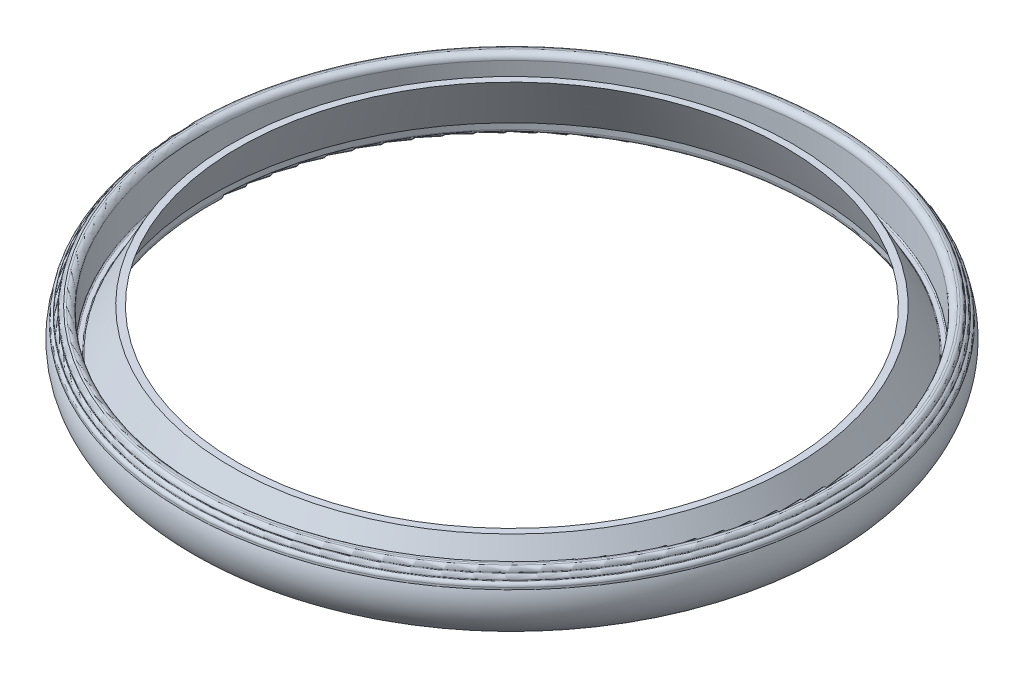
SolidWorks part; units mm, degrees
material "Plain Carbon Steel"
ref_plane "Front Plane" through (0, 0, 0) normal (0, 0, 1) x (1, 0, 0)
ref_plane "Top Plane" through (0, 0, 0) normal (0, 1, 0) x (1, 0, 0)
ref_plane "Right Plane" through (0, 0, 0) normal (1, 0, 0) x (0, 0, -1)
sketch "Sketch1" plane through (0, 0, 0) normal (0, 0, 1) x (1, 0, 0)
  line L0 (0, 0) -> (0, 28.829) construction
  line L1 (0, 0) -> (-132.08, 0)
  line L2 (-132.08, 0) -> (-132.08, 5.08)
  line L3 (-132.08, 5.08) -> (0, 5.08)
  line L4 (-132.08, 2.54) -> (0, 2.54)
  line L6 (-132.08, 5.08) -> (-120.4455, 28.829)
  line L7 (-136.0959, 28.829) -> (-136.0959, 10.2616)
  line L9 (-123.4775, 28.829) -> (-133.5588, 10.2616)
  line L11 (-136.0959, 10.2616) -> (-133.5588, 10.2616)
  line L12 (-141.2578, 28.3446) -> (-141.3495, 26.5944)
  line L13 (-136.0959, 28.7962) -> (-141.2578, 28.3446)
  line L14 (-141.3495, 26.5944) -> (-142.7159, 26.4749)
  line L15 (-142.7159, 26.4749) -> (-142.8116, 24.6486)
  line L16 (-142.8116, 24.6486) -> (-144.0515, 24.5401)
  line L17 (-144.0515, 24.5401) -> (-144.1764, 22.1558)
  line L20 (-120.4455, 28.829) -> (-123.4775, 28.829)
  arc A1 (-144.1764, 22.1558) -> (-134.62, 0) centre (-127.7896, 16.085) ccw
  arc A2 (-132.08, 2.54) -> (-134.62, 0) centre (-134.62, 2.54) cw
revolve "Revolve1" add sketch "Sketch1" angle 360 about L0 region at (-136.2759, 15.0017, 0)
fillet "Fillet1" radius 0.508 2 edges at (0, 10.2616, -133.5588) (0, 10.2616, -136.0959)
fillet "Fillet2" radius 2.54 1 edges at (0, 28.7962, -136.0959)
fillet "Fillet3" radius 1.778 3 edges at (0, 24.5401, -144.0515) (0, 26.4749, -142.7159) (0, 28.3446, -141.2578)
fillet "Fillet4" radius 0.254 2 edges at (0, 24.6486, -142.8116) (0, 26.5944, -141.3495)
